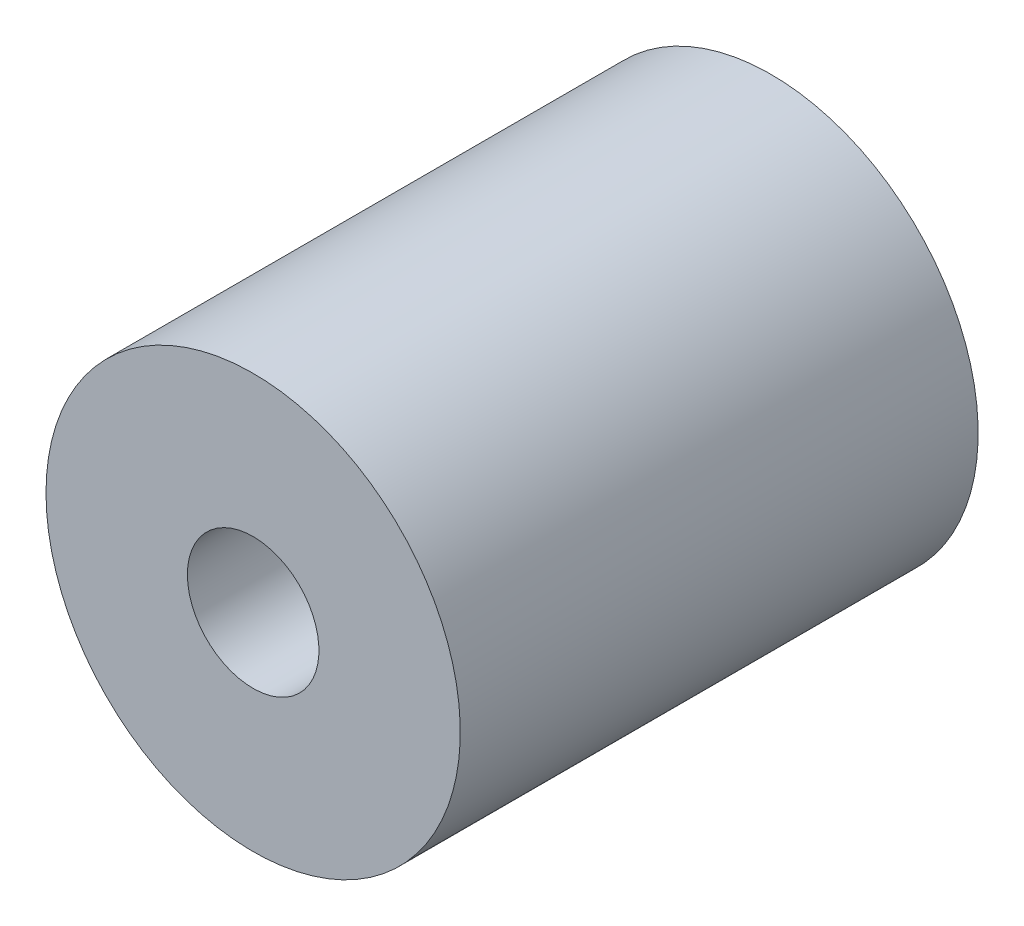
SolidWorks part; units mm, degrees
ref_plane "Front Plane" through (0, 0, 0) normal (0, 0, 1) x (1, 0, 0)
ref_plane "Top Plane" through (0, 0, 0) normal (0, 1, 0) x (1, 0, 0)
ref_plane "Right Plane" through (0, 0, 0) normal (1, 0, 0) x (0, 0, -1)
ref_plane "Plane1" through (0, 0, 25) normal (0, 0, 1) x (1, 0, 0)
sketch "Sketch1" plane through (0, 0, 25) normal (0, 0, 1) x (1, 0, 0)
  circle A0 centre (0, 0) radius 10
extrude "Boss-Extrude1" add sketch "Sketch1" against normal blind 25
sketch "Sketch2" plane through (0, 0, 25) normal (0, 0, 1) x (1, 0, 0)
  circle A0 centre (0, 0) radius 3.175
extrude "Cut-Extrude1" cut sketch "Sketch2" against normal blind 12.5
sketch "Sketch3" plane through (0, 0, 0) normal (0, 0, -1) x (-1, 0, 0)
  circle A0 centre (0, 0) radius 2.5
extrude "Cut-Extrude2" cut sketch "Sketch3" against normal through all
ref_axis "Axis1" through (0, 0, -6.668) along (0, 0, 1)
